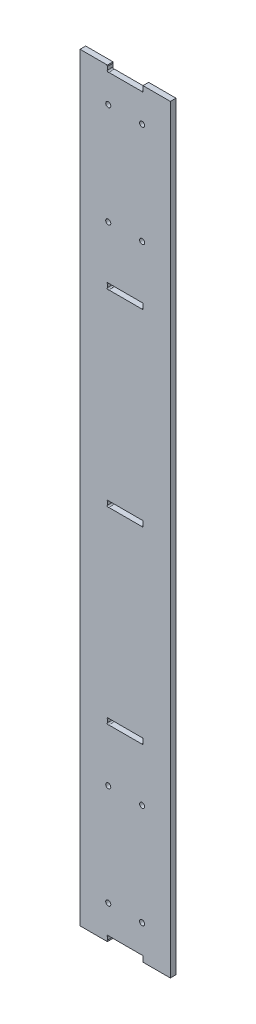
SolidWorks part; units mm, degrees
material "Acrylic (Medium-high impact)"
ref_plane "Front Plane" through (0, 0, 0) normal (0, 0, 1) x (1, 0, 0)
ref_plane "Top Plane" through (0, 0, 0) normal (0, 1, 0) x (1, 0, 0)
ref_plane "Right Plane" through (0, 0, 0) normal (1, 0, 0) x (0, 0, -1)
sketch "Sketch1" plane through (0, 0, 0) normal (0, 1, 0) x (1, 0, 0)
  line L0 (0, 0) -> (0, 76.2) construction
  line L2 (25.4, 68.667) -> (-25.4, 68.667)
  line L3 (25.4, 68.667) -> (25.4, 71.842)
  line L4 (25.4, 71.842) -> (-25.4, 71.842)
  line L5 (-25.4, 68.667) -> (-25.4, 71.842)
  line L6 (25.4, 68.667) -> (-25.4, 71.842) construction
  line L7 (25.4, 71.842) -> (-25.4, 68.667) construction
  circle A0 centre (0, 0) radius 76.2 construction
  point P4 (0, 70.2545)
  dimension "D1" = 152.4
  dimension "D2" = 3.175
  dimension "D3" = 50.8
extrude "Boss-Extrude1" add sketch "Sketch1" along normal blind 427.1518
sketch "Sketch2" plane through (0, 0, -68.667) normal (0, 0, 1) x (1, 0, 0)
  line L1 (-25.4, 427.1518) -> (25.4, 427.1518)
  line L2 (-25.4, 427.1518) -> (-25.4, 0)
  line L3 (-25.4, 0) -> (25.4, 0)
  line L4 (25.4, 427.1518) -> (25.4, 0)
sketch "Sketch3" plane through (0, 0, -68.667) normal (0, 0, 1) x (1, 0, 0)
  line L0 (0, 427.1518) -> (0, 0) construction
  line L1 (-25.4, 427.1518) -> (25.4, 427.1518) construction
  line L2 (-25.4, 0) -> (25.4, 0) construction
  line L3 (-25.4, 213.5759) -> (25.4, 213.5759) construction
  line L4 (-25.4, 427.1518) -> (-25.4, 0) construction
  line L5 (25.4, 427.1518) -> (25.4, 0) construction
  circle A0 centre (-19.05, 376.3518) radius 1.4224
  circle A1 centre (-12.7, 376.3518) radius 1.4224
  circle A2 centre (-6.35, 376.3518) radius 1.4224
  circle A3 centre (0, 376.3518) radius 1.4224
  circle A4 centre (6.35, 376.3518) radius 1.4224
  circle A5 centre (12.7, 376.3518) radius 1.4224
  circle A6 centre (19.05, 376.3518) radius 1.4224
  circle A7 centre (-12.7, 370.0018) radius 1.4224
  circle A8 centre (-6.35, 370.0018) radius 1.4224
  circle A9 centre (0, 370.0018) radius 1.4224
  circle A10 centre (6.35, 370.0018) radius 1.4224
  circle A11 centre (12.7, 370.0018) radius 1.4224
  circle A12 centre (19.05, 370.0018) radius 1.4224
  circle A13 centre (-12.7, 363.6518) radius 1.4224
  circle A14 centre (-6.35, 363.6518) radius 1.4224
  circle A15 centre (0, 363.6518) radius 1.4224
  circle A16 centre (6.35, 363.6518) radius 1.4224
  circle A17 centre (12.7, 363.6518) radius 1.4224
  circle A18 centre (19.05, 363.6518) radius 1.4224
  circle A19 centre (-12.7, 357.3018) radius 1.4224
  circle A20 centre (-6.35, 357.3018) radius 1.4224
  circle A21 centre (0, 357.3018) radius 1.4224
  circle A22 centre (6.35, 357.3018) radius 1.4224
  circle A23 centre (12.7, 357.3018) radius 1.4224
  circle A24 centre (19.05, 357.3018) radius 1.4224
  circle A25 centre (-12.7, 350.9518) radius 1.4224
  circle A26 centre (-6.35, 350.9518) radius 1.4224
  circle A27 centre (0, 350.9518) radius 1.4224
  circle A28 centre (6.35, 350.9518) radius 1.4224
  circle A29 centre (12.7, 350.9518) radius 1.4224
  circle A30 centre (19.05, 350.9518) radius 1.4224
  circle A31 centre (-12.7, 344.6018) radius 1.4224
  circle A32 centre (-6.35, 344.6018) radius 1.4224
  circle A33 centre (0, 344.6018) radius 1.4224
  circle A34 centre (6.35, 344.6018) radius 1.4224
  circle A35 centre (12.7, 344.6018) radius 1.4224
  circle A36 centre (19.05, 344.6018) radius 1.4224
  circle A37 centre (-12.7, 338.2518) radius 1.4224
  circle A38 centre (-6.35, 338.2518) radius 1.4224
  circle A39 centre (0, 338.2518) radius 1.4224
  circle A40 centre (6.35, 338.2518) radius 1.4224
  circle A41 centre (12.7, 338.2518) radius 1.4224
  circle A42 centre (19.05, 338.2518) radius 1.4224
  circle A43 centre (-12.7, 331.9018) radius 1.4224
  circle A44 centre (-6.35, 331.9018) radius 1.4224
  circle A45 centre (0, 331.9018) radius 1.4224
  circle A46 centre (6.35, 331.9018) radius 1.4224
  circle A47 centre (12.7, 331.9018) radius 1.4224
  circle A48 centre (19.05, 331.9018) radius 1.4224
  circle A49 centre (-19.05, 370.0018) radius 1.4224
  circle A50 centre (-19.05, 363.6518) radius 1.4224
  circle A51 centre (-19.05, 357.3018) radius 1.4224
  circle A52 centre (-19.05, 350.9518) radius 1.4224
  circle A53 centre (-19.05, 344.6018) radius 1.4224
  circle A54 centre (-19.05, 338.2518) radius 1.4224
  circle A55 centre (-19.05, 331.9018) radius 1.4224
  circle A56 centre (-19.05, 325.5518) radius 1.4224
  circle A57 centre (-12.7, 325.5518) radius 1.4224
  circle A58 centre (-6.35, 325.5518) radius 1.4224
  circle A59 centre (0, 325.5518) radius 1.4224
  circle A60 centre (6.35, 325.5518) radius 1.4224
  circle A61 centre (12.7, 325.5518) radius 1.4224
  circle A62 centre (19.05, 325.5518) radius 1.4224
  circle A63 centre (-19.05, 319.2018) radius 1.4224
  circle A64 centre (-12.7, 319.2018) radius 1.4224
  circle A65 centre (-6.35, 319.2018) radius 1.4224
  circle A66 centre (0, 319.2018) radius 1.4224
  circle A67 centre (6.35, 319.2018) radius 1.4224
  circle A68 centre (12.7, 319.2018) radius 1.4224
  circle A69 centre (19.05, 319.2018) radius 1.4224
  circle A70 centre (-19.05, 312.8518) radius 1.4224
  circle A71 centre (-12.7, 312.8518) radius 1.4224
  circle A72 centre (-6.35, 312.8518) radius 1.4224
  circle A73 centre (0, 312.8518) radius 1.4224
  circle A74 centre (6.35, 312.8518) radius 1.4224
  circle A75 centre (12.7, 312.8518) radius 1.4224
  circle A76 centre (19.05, 312.8518) radius 1.4224
  circle A77 centre (-19.05, 306.5018) radius 1.4224
  circle A78 centre (-12.7, 306.5018) radius 1.4224
  circle A79 centre (-6.35, 306.5018) radius 1.4224
  circle A80 centre (0, 306.5018) radius 1.4224
  circle A81 centre (6.35, 306.5018) radius 1.4224
  circle A82 centre (12.7, 306.5018) radius 1.4224
  circle A83 centre (19.05, 306.5018) radius 1.4224
  circle A84 centre (-19.05, 300.1518) radius 1.4224
  circle A85 centre (-12.7, 300.1518) radius 1.4224
  circle A86 centre (-6.35, 300.1518) radius 1.4224
  circle A87 centre (0, 300.1518) radius 1.4224
  circle A88 centre (6.35, 300.1518) radius 1.4224
  circle A89 centre (12.7, 300.1518) radius 1.4224
  circle A90 centre (19.05, 300.1518) radius 1.4224
  circle A91 centre (-19.05, 293.8018) radius 1.4224
  circle A92 centre (-12.7, 293.8018) radius 1.4224
  circle A93 centre (-6.35, 293.8018) radius 1.4224
  circle A94 centre (0, 293.8018) radius 1.4224
  circle A95 centre (6.35, 293.8018) radius 1.4224
  circle A96 centre (12.7, 293.8018) radius 1.4224
  circle A97 centre (19.05, 293.8018) radius 1.4224
  circle A98 centre (-19.05, 287.4518) radius 1.4224
  circle A99 centre (-12.7, 287.4518) radius 1.4224
  circle A100 centre (-6.35, 287.4518) radius 1.4224
  circle A101 centre (0, 287.4518) radius 1.4224
  circle A102 centre (6.35, 287.4518) radius 1.4224
  circle A103 centre (12.7, 287.4518) radius 1.4224
  circle A104 centre (19.05, 287.4518) radius 1.4224
  circle A105 centre (19.05, 139.7) radius 1.4224
  circle A106 centre (12.7, 139.7) radius 1.4224
  circle A107 centre (6.35, 139.7) radius 1.4224
  circle A108 centre (0, 139.7) radius 1.4224
  circle A109 centre (-6.35, 139.7) radius 1.4224
  circle A110 centre (-12.7, 139.7) radius 1.4224
  circle A111 centre (-19.05, 139.7) radius 1.4224
  circle A112 centre (19.05, 133.35) radius 1.4224
  circle A113 centre (12.7, 133.35) radius 1.4224
  circle A114 centre (6.35, 133.35) radius 1.4224
  circle A115 centre (0, 133.35) radius 1.4224
  circle A116 centre (-6.35, 133.35) radius 1.4224
  circle A117 centre (-12.7, 133.35) radius 1.4224
  circle A118 centre (-19.05, 133.35) radius 1.4224
  circle A119 centre (19.05, 127) radius 1.4224
  circle A120 centre (12.7, 127) radius 1.4224
  circle A121 centre (6.35, 127) radius 1.4224
  circle A122 centre (0, 127) radius 1.4224
  circle A123 centre (-6.35, 127) radius 1.4224
  circle A124 centre (-12.7, 127) radius 1.4224
  circle A125 centre (-19.05, 127) radius 1.4224
  circle A126 centre (19.05, 120.65) radius 1.4224
  circle A127 centre (12.7, 120.65) radius 1.4224
  circle A128 centre (6.35, 120.65) radius 1.4224
  circle A129 centre (0, 120.65) radius 1.4224
  circle A130 centre (-6.35, 120.65) radius 1.4224
  circle A131 centre (-12.7, 120.65) radius 1.4224
  circle A132 centre (-19.05, 120.65) radius 1.4224
  circle A133 centre (19.05, 114.3) radius 1.4224
  circle A134 centre (12.7, 114.3) radius 1.4224
  circle A135 centre (6.35, 114.3) radius 1.4224
  circle A136 centre (0, 114.3) radius 1.4224
  circle A137 centre (-6.35, 114.3) radius 1.4224
  circle A138 centre (-12.7, 114.3) radius 1.4224
  circle A139 centre (-19.05, 114.3) radius 1.4224
  circle A140 centre (19.05, 107.95) radius 1.4224
  circle A141 centre (12.7, 107.95) radius 1.4224
  circle A142 centre (6.35, 107.95) radius 1.4224
  circle A143 centre (0, 107.95) radius 1.4224
  circle A144 centre (-6.35, 107.95) radius 1.4224
  circle A145 centre (-12.7, 107.95) radius 1.4224
  circle A146 centre (-19.05, 107.95) radius 1.4224
  circle A147 centre (19.05, 101.6) radius 1.4224
  circle A148 centre (12.7, 101.6) radius 1.4224
  circle A149 centre (6.35, 101.6) radius 1.4224
  circle A150 centre (0, 101.6) radius 1.4224
  circle A151 centre (-6.35, 101.6) radius 1.4224
  circle A152 centre (-12.7, 101.6) radius 1.4224
  circle A153 centre (-19.05, 101.6) radius 1.4224
  circle A154 centre (-19.05, 95.25) radius 1.4224
  circle A155 centre (-19.05, 88.9) radius 1.4224
  circle A156 centre (-19.05, 82.55) radius 1.4224
  circle A157 centre (-19.05, 76.2) radius 1.4224
  circle A158 centre (-19.05, 69.85) radius 1.4224
  circle A159 centre (-19.05, 63.5) radius 1.4224
  circle A160 centre (-19.05, 57.15) radius 1.4224
  circle A161 centre (19.05, 95.25) radius 1.4224
  circle A162 centre (12.7, 95.25) radius 1.4224
  circle A163 centre (6.35, 95.25) radius 1.4224
  circle A164 centre (0, 95.25) radius 1.4224
  circle A165 centre (-6.35, 95.25) radius 1.4224
  circle A166 centre (-12.7, 95.25) radius 1.4224
  circle A167 centre (19.05, 88.9) radius 1.4224
  circle A168 centre (12.7, 88.9) radius 1.4224
  circle A169 centre (6.35, 88.9) radius 1.4224
  circle A170 centre (0, 88.9) radius 1.4224
  circle A171 centre (-6.35, 88.9) radius 1.4224
  circle A172 centre (-12.7, 88.9) radius 1.4224
  circle A173 centre (19.05, 82.55) radius 1.4224
  circle A174 centre (12.7, 82.55) radius 1.4224
  circle A175 centre (6.35, 82.55) radius 1.4224
  circle A176 centre (0, 82.55) radius 1.4224
  circle A177 centre (-6.35, 82.55) radius 1.4224
  circle A178 centre (-12.7, 82.55) radius 1.4224
  circle A179 centre (19.05, 76.2) radius 1.4224
  circle A180 centre (12.7, 76.2) radius 1.4224
  circle A181 centre (6.35, 76.2) radius 1.4224
  circle A182 centre (0, 76.2) radius 1.4224
  circle A183 centre (-6.35, 76.2) radius 1.4224
  circle A184 centre (-12.7, 76.2) radius 1.4224
  circle A185 centre (19.05, 69.85) radius 1.4224
  circle A186 centre (12.7, 69.85) radius 1.4224
  circle A187 centre (6.35, 69.85) radius 1.4224
  circle A188 centre (0, 69.85) radius 1.4224
  circle A189 centre (-6.35, 69.85) radius 1.4224
  circle A190 centre (-12.7, 69.85) radius 1.4224
  circle A191 centre (19.05, 63.5) radius 1.4224
  circle A192 centre (12.7, 63.5) radius 1.4224
  circle A193 centre (6.35, 63.5) radius 1.4224
  circle A194 centre (0, 63.5) radius 1.4224
  circle A195 centre (-6.35, 63.5) radius 1.4224
  circle A196 centre (-12.7, 63.5) radius 1.4224
  circle A197 centre (19.05, 57.15) radius 1.4224
  circle A198 centre (12.7, 57.15) radius 1.4224
  circle A199 centre (6.35, 57.15) radius 1.4224
  circle A200 centre (0, 57.15) radius 1.4224
  circle A201 centre (-6.35, 57.15) radius 1.4224
  circle A202 centre (-12.7, 57.15) radius 1.4224
  circle A203 centre (19.05, 50.8) radius 1.4224
  circle A204 centre (12.7, 50.8) radius 1.4224
  circle A205 centre (6.35, 50.8) radius 1.4224
  circle A206 centre (0, 50.8) radius 1.4224
  circle A207 centre (-6.35, 50.8) radius 1.4224
  circle A208 centre (-12.7, 50.8) radius 1.4224
  circle A209 centre (-19.05, 50.8) radius 1.4224
  dimension "D1" = 2.8448
  dimension "D2" = 6.35
  dimension "D3" = 50.8
  dimension "D4" = 7
  dimension "D5" = 8
  dimension "D6" = 8
sketch "Sketch4" plane through (0, 0, -68.667) normal (0, 0, 1) x (1, 0, 0)
  line L0 (0, 427.1518) -> (0, 0) construction
  line L1 (-25.4, 427.1518) -> (25.4, 427.1518) construction
  line L2 (-25.4, 0) -> (25.4, 0) construction
  circle A0 centre (-3.175, 376.3518) radius 1.4224
  circle A2 centre (-9.525, 376.3518) radius 1.4224
  circle A4 centre (-9.525, 370.0018) radius 1.4224
  circle A6 centre (-9.525, 363.6518) radius 1.4224
  circle A8 centre (-9.525, 357.3018) radius 1.4224
  circle A10 centre (-9.525, 350.9518) radius 1.4224
  circle A12 centre (-9.525, 344.6018) radius 1.4224
  circle A14 centre (-9.525, 338.2518) radius 1.4224
  circle A16 centre (-9.525, 331.9018) radius 1.4224
  circle A18 centre (-9.525, 325.5518) radius 1.4224
  circle A20 centre (-9.525, 319.2018) radius 1.4224
  circle A22 centre (-9.525, 312.8518) radius 1.4224
  circle A24 centre (-9.525, 306.5018) radius 1.4224
  circle A26 centre (-9.525, 300.1518) radius 1.4224
  circle A28 centre (-9.525, 293.8018) radius 1.4224
  circle A30 centre (-9.525, 287.4518) radius 1.4224
  circle A32 centre (-9.525, 281.1018) radius 1.4224
  circle A34 centre (-3.175, 370.0018) radius 1.4224
  circle A35 centre (-3.175, 363.6518) radius 1.4224
  circle A36 centre (-3.175, 357.3018) radius 1.4224
  circle A37 centre (-3.175, 350.9518) radius 1.4224
  circle A38 centre (-3.175, 344.6018) radius 1.4224
  circle A39 centre (-3.175, 338.2518) radius 1.4224
  circle A40 centre (-3.175, 331.9018) radius 1.4224
  circle A41 centre (-3.175, 325.5518) radius 1.4224
  circle A42 centre (-3.175, 319.2018) radius 1.4224
  circle A43 centre (-3.175, 312.8518) radius 1.4224
  circle A44 centre (-3.175, 306.5018) radius 1.4224
  circle A45 centre (-3.175, 300.1518) radius 1.4224
  circle A46 centre (-3.175, 293.8018) radius 1.4224
  circle A47 centre (-3.175, 287.4518) radius 1.4224
  circle A48 centre (-3.175, 281.1018) radius 1.4224
  circle A49 centre (3.175, 281.1018) radius 1.4224
  circle A50 centre (3.175, 287.4518) radius 1.4224
  circle A51 centre (3.175, 293.8018) radius 1.4224
  circle A52 centre (3.175, 300.1518) radius 1.4224
  circle A53 centre (3.175, 306.5018) radius 1.4224
  circle A54 centre (3.175, 312.8518) radius 1.4224
  circle A55 centre (3.175, 319.2018) radius 1.4224
  circle A56 centre (3.175, 325.5518) radius 1.4224
  circle A57 centre (3.175, 331.9018) radius 1.4224
  circle A58 centre (3.175, 338.2518) radius 1.4224
  circle A59 centre (3.175, 344.6018) radius 1.4224
  circle A60 centre (3.175, 350.9518) radius 1.4224
  circle A61 centre (3.175, 357.3018) radius 1.4224
  circle A62 centre (3.175, 363.6518) radius 1.4224
  circle A63 centre (3.175, 370.0018) radius 1.4224
  circle A65 centre (9.525, 281.1018) radius 1.4224
  circle A67 centre (9.525, 287.4518) radius 1.4224
  circle A69 centre (9.525, 293.8018) radius 1.4224
  circle A71 centre (9.525, 300.1518) radius 1.4224
  circle A73 centre (9.525, 306.5018) radius 1.4224
  circle A75 centre (9.525, 312.8518) radius 1.4224
  circle A77 centre (9.525, 319.2018) radius 1.4224
  circle A79 centre (9.525, 325.5518) radius 1.4224
  circle A81 centre (9.525, 331.9018) radius 1.4224
  circle A83 centre (9.525, 338.2518) radius 1.4224
  circle A85 centre (9.525, 344.6018) radius 1.4224
  circle A87 centre (9.525, 350.9518) radius 1.4224
  circle A89 centre (9.525, 357.3018) radius 1.4224
  circle A91 centre (9.525, 363.6518) radius 1.4224
  circle A93 centre (9.525, 370.0018) radius 1.4224
  circle A95 centre (9.525, 376.3518) radius 1.4224
  circle A96 centre (3.175, 376.3518) radius 1.4224
  circle A97 centre (-9.525, 382.7018) radius 1.4224
  circle A100 centre (9.525, 382.7018) radius 1.4224
  circle A103 centre (-9.525, 389.0518) radius 1.4224
  circle A106 centre (9.525, 389.0518) radius 1.4224
  circle A109 centre (-9.525, 395.4018) radius 1.4224
  circle A112 centre (9.525, 395.4018) radius 1.4224
  circle A115 centre (-9.525, 401.7518) radius 1.4224
  circle A118 centre (9.525, 401.7518) radius 1.4224
  circle A121 centre (-9.525, 408.1018) radius 1.4224
  circle A124 centre (9.525, 408.1018) radius 1.4224
  circle A127 centre (-9.525, 414.4518) radius 1.4224
  circle A130 centre (9.525, 414.4518) radius 1.4224
  circle A144 centre (-3.175, 382.7018) radius 1.4224 [skipped]
  circle A145 centre (-3.175, 389.0518) radius 1.4224 [skipped]
  circle A146 centre (-3.175, 395.4018) radius 1.4224 [skipped]
  circle A147 centre (-3.175, 401.7518) radius 1.4224 [skipped]
  circle A148 centre (-3.175, 408.1018) radius 1.4224 [skipped]
  circle A149 centre (-3.175, 414.4518) radius 1.4224 [skipped]
  circle A150 centre (3.175, 382.7018) radius 1.4224 [skipped]
  circle A151 centre (3.175, 389.0518) radius 1.4224 [skipped]
  circle A152 centre (3.175, 395.4018) radius 1.4224 [skipped]
  circle A153 centre (3.175, 401.7518) radius 1.4224 [skipped]
  circle A154 centre (3.175, 408.1018) radius 1.4224 [skipped]
  circle A155 centre (3.175, 414.4518) radius 1.4224 [skipped]
  circle A156 centre (-15.875, 363.6518) radius 1.4224 [skipped]
  circle A157 centre (-15.875, 357.3018) radius 1.4224 [skipped]
  circle A158 centre (-15.875, 350.9518) radius 1.4224 [skipped]
  circle A159 centre (-15.875, 344.6018) radius 1.4224 [skipped]
  circle A160 centre (-15.875, 338.2518) radius 1.4224 [skipped]
  circle A161 centre (-15.875, 331.9018) radius 1.4224 [skipped]
  circle A162 centre (-15.875, 325.5518) radius 1.4224 [skipped]
  circle A163 centre (-15.875, 319.2018) radius 1.4224 [skipped]
  circle A164 centre (-15.875, 312.8518) radius 1.4224 [skipped]
  circle A165 centre (-15.875, 306.5018) radius 1.4224 [skipped]
  circle A166 centre (-15.875, 300.1518) radius 1.4224 [skipped]
  circle A167 centre (-15.875, 293.8018) radius 1.4224 [skipped]
  circle A168 centre (-15.875, 287.4518) radius 1.4224 [skipped]
  circle A169 centre (-15.875, 281.1018) radius 1.4224 [skipped]
  circle A170 centre (-15.875, 376.3518) radius 1.4224 [skipped]
  circle A171 centre (-15.875, 370.0018) radius 1.4224 [skipped]
  dimension "D2" = 2.8448
  dimension "D1" = 3.175
  dimension "D3" = 50.8
  dimension "D4" = 3
  dimension "D5" = 16
  dimension "D7" = 7
extrude "Cut-Extrude2" cut sketch "Sketch4" against normal blind 5.08
sketch "Sketch5" plane through (0, 0, -68.667) normal (0, 0, 1) x (1, 0, 0)
  line L1 (-6.4666, 378.8778) -> (6.1161, 378.8778)
  line L2 (-6.4666, 378.8778) -> (-6.4666, 277.848)
  line L3 (-6.4666, 277.848) -> (6.1161, 277.848)
  line L4 (6.1161, 378.8778) -> (6.1161, 277.848)
extrude "Boss-Extrude2" add sketch "Sketch5" against normal blind 3.175
sketch "Sketch6" plane through (0, 0, -68.667) normal (0, 0, 1) x (1, 0, 0)
  line L1 (-20.2574, 381.0412) -> (-12.7108, 381.0412)
  line L2 (-20.2574, 381.0412) -> (-20.2574, 272.3701)
  line L3 (-20.2574, 272.3701) -> (-12.7108, 272.3701)
  line L4 (-12.7108, 381.0412) -> (-12.7108, 272.3701)
  line L5 (12.4446, 381.0412) -> (21.5005, 381.0412)
  line L6 (12.4446, 381.0412) -> (12.4446, 272.3701)
  line L7 (12.4446, 272.3701) -> (21.5005, 272.3701)
  line L8 (21.5005, 381.0412) -> (21.5005, 272.3701)
extrude "Boss-Extrude3" add sketch "Sketch6" against normal blind 3.175
sketch "Sketch7" plane through (0, 0, -68.667) normal (0, 0, 1) x (1, 0, 0)
  line L0 (25.4, 427.1518) -> (25.4, 0) construction
  line L1 (-25.4, 427.1518) -> (25.4, 427.1518)
  line L2 (-25.4, 427.1518) -> (-25.4, 410.6418)
  line L3 (-25.4, 410.6418) -> (25.4, 410.6418)
  line L4 (25.4, 427.1518) -> (25.4, 410.6418)
  dimension "D1" = 16.51
extrude "Boss-Extrude4" add sketch "Sketch7" against normal blind 3.175
sketch "Sketch8" plane through (0, 0, -68.667) normal (0, 0, 1) x (1, 0, 0)
  line L0 (-25.4, 427.1518) -> (-25.4, 0) construction
  line L1 (-25.4, 404.9269) -> (25.4, 404.9269)
  line L2 (-25.4, 404.9269) -> (-25.4, 353.7389)
  line L3 (-25.4, 353.7389) -> (25.4, 353.7389)
  line L4 (25.4, 404.9269) -> (25.4, 353.7389)
  line L5 (25.4, 427.1518) -> (25.4, 0) construction
extrude "Boss-Extrude5" add sketch "Sketch8" against normal blind 3.175
sketch "Sketch9" plane through (0, 0, -68.667) normal (0, 0, 1) x (1, 0, 0)
  line L0 (-25.4, 427.1518) -> (-25.4, 0) construction
  line L1 (-25.4, 347.6) -> (25.4, 347.6)
  line L2 (-25.4, 347.6) -> (-25.4, 277.4309)
  line L3 (-25.4, 277.4309) -> (25.4, 277.4309)
  line L4 (25.4, 347.6) -> (25.4, 277.4309)
  line L5 (25.4, 427.1518) -> (25.4, 0) construction
extrude "Boss-Extrude6" add sketch "Sketch9" against normal blind 3.175
sketch "Sketch10" plane through (0, 0, -68.667) normal (0, 0, 1) x (1, 0, 0)
  line L0 (-25.4, 213.5759) -> (25.4, 213.5759) construction
  line L1 (-25.4, 427.1518) -> (-25.4, 0) construction
  line L2 (25.4, 427.1518) -> (25.4, 0) construction
ref_plane "Plane1" through (0, 213.5759, 0) normal (0, 1, 0) x (1, 0, 0)
mirror "Mirror1" about plane through (0, 213.5759, 0) normal (0, 1, 0) of "Boss-Extrude4", "Boss-Extrude6", "Boss-Extrude5", "Boss-Extrude3", "Boss-Extrude2", "Cut-Extrude2"
sketch "Sketch11" plane through (0, 0, -68.667) normal (0, 0, 1) x (1, 0, 0)
  line L0 (25.4, 0) -> (-25.4, 0) construction
  line L1 (-25.4, 213.5759) -> (25.4, 213.5759) construction
  line L2 (-25.4, 427.1518) -> (-25.4, 0) construction
  line L3 (25.4, 427.1518) -> (25.4, 0) construction
  line L4 (-9.6464, 2.8214) -> (9.6464, 0.3536) construction
  line L5 (9.2929, 105.9942) -> (-9.2929, 105.9942)
  line L6 (10, 106.7013) -> (10, 108.4621)
  line L7 (9.2929, 109.1692) -> (-9.2929, 109.1692)
  line L8 (10, 3.175) -> (10, 2.4679) construction
  line L9 (9.2929, 0) -> (-9.2929, 0)
  line L10 (10, 0.7071) -> (10, 2.4679)
  line L11 (9.2929, 3.175) -> (-9.2929, 3.175)
  line L12 (-10, 0.7071) -> (-10, 2.4679)
  line L13 (10, 3.175) -> (9.2929, 3.175) construction
  line L14 (10, 0.7071) -> (10, 0) construction
  line L15 (10, 0) -> (9.2929, 0) construction
  line L16 (-9.2929, 0) -> (-10, 0) construction
  line L17 (-10, 0) -> (-10, 0.7071) construction
  line L18 (-10, 2.4679) -> (-10, 3.175) construction
  line L19 (-10, 3.175) -> (-9.2929, 3.175) construction
  line L20 (-25.4, 0) -> (25.4, 0) construction
  line L21 (-10, 106.7013) -> (-10, 108.4621)
  line L22 (-9.6464, 108.8156) -> (9.6464, 106.3478) construction
  line L23 (10, 109.1692) -> (10, 108.4621) construction
  line L24 (10, 109.1692) -> (9.2929, 109.1692) construction
  line L25 (10, 106.7013) -> (10, 105.9942) construction
  line L26 (10, 105.9942) -> (9.2929, 105.9942) construction
  line L27 (-9.2929, 105.9942) -> (-10, 105.9942) construction
  line L28 (-10, 105.9942) -> (-10, 106.7013) construction
  line L29 (-10, 108.4621) -> (-10, 109.1692) construction
  line L30 (-10, 109.1692) -> (-9.2929, 109.1692) construction
  line L31 (9.2929, 211.9884) -> (-9.2929, 211.9884)
  line L32 (10, 212.6955) -> (10, 214.4563)
  line L33 (9.2929, 215.1634) -> (-9.2929, 215.1634)
  line L34 (-10, 212.6955) -> (-10, 214.4563)
  line L35 (-9.6464, 214.8098) -> (9.6464, 212.342) construction
  line L36 (10, 215.1634) -> (10, 214.4563) construction
  line L37 (10, 215.1634) -> (9.2929, 215.1634) construction
  line L38 (10, 212.6955) -> (10, 211.9884) construction
  line L39 (10, 211.9884) -> (9.2929, 211.9884) construction
  line L40 (-9.2929, 211.9884) -> (-10, 211.9884) construction
  line L41 (-10, 211.9884) -> (-10, 212.6955) construction
  line L42 (-10, 214.4563) -> (-10, 215.1634) construction
  line L43 (-10, 215.1634) -> (-9.2929, 215.1634) construction
  arc A0 (10, 2.4679) -> (9.2929, 3.175) centre (9.6464, 2.8214) ccw
  arc A1 (10, 0.7071) -> (9.2929, 0) centre (9.6464, 0.3536) cw
  arc A2 (-9.2929, 0) -> (-10, 0.7071) centre (-9.6464, 0.3536) cw
  arc A3 (-10, 2.4679) -> (-9.2929, 3.175) centre (-9.6464, 2.8214) cw
  arc A4 (10, 108.4621) -> (9.2929, 109.1692) centre (9.6464, 108.8156) ccw
  arc A5 (10, 106.7013) -> (9.2929, 105.9942) centre (9.6464, 106.3478) cw
  arc A6 (-9.2929, 105.9942) -> (-10, 106.7013) centre (-9.6464, 106.3478) cw
  arc A7 (-10, 108.4621) -> (-9.2929, 109.1692) centre (-9.6464, 108.8156) cw
  arc A8 (10, 214.4563) -> (9.2929, 215.1634) centre (9.6464, 214.8098) ccw
  arc A9 (10, 212.6955) -> (9.2929, 211.9884) centre (9.6464, 212.342) cw
  arc A10 (-9.2929, 211.9884) -> (-10, 212.6955) centre (-9.6464, 212.342) cw
  arc A11 (-10, 214.4563) -> (-9.2929, 215.1634) centre (-9.6464, 214.8098) cw
  point P2 (0, 0)
  point P3 (0, 0)
  point P11 (0, 213.5759)
  point P29 (-25.4, 213.5759)
  point P32 (25.4, 213.5759)
  point P63 (0, 213.5759)
  dimension "D1" = 0.5
  dimension "D2" = 20
  dimension "D4" = 3.175
  dimension "D3" = 3
extrude "Cut-Extrude3" cut sketch "Sketch11" against normal through all
ref_plane "Plane2" through (0, 213.5759, 0) normal (0, -1, 0) x (-1, 0, 0)
mirror "Mirror2" about plane through (0, 213.5759, 0) normal (0, -1, 0) of "Cut-Extrude3"
